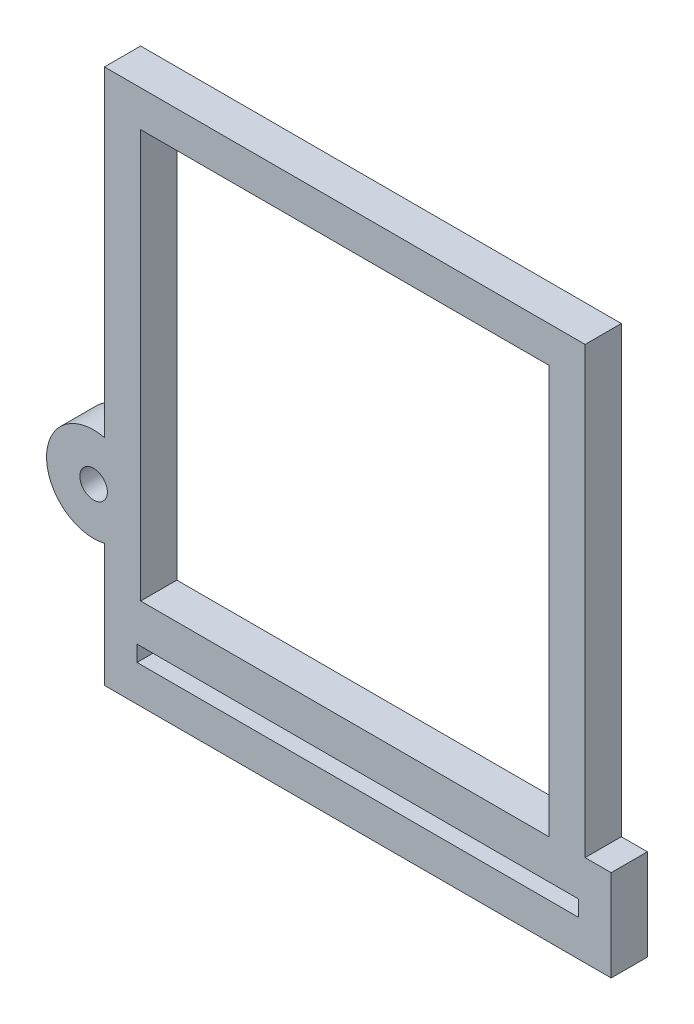
SolidWorks part; units mm, degrees
ref_plane "Спереди" through (0, 0, 0) normal (0, 0, 1) x (1, 0, 0)
ref_plane "Сверху" through (0, 0, 0) normal (0, 1, 0) x (1, 0, 0)
ref_plane "Справа" through (0, 0, 0) normal (1, 0, 0) x (0, 0, -1)
sketch "Эскиз1" plane through (0, 0, 0) normal (0, 0, 1) x (1, 0, 0)
  line L1 (0, 0) -> (70, 0)
  line L2 (0, 0) -> (0, 74)
  line L3 (0, 74) -> (70, 74)
  line L4 (70, 0) -> (70, 74)
  dimension "D1" = 74
  dimension "D2" = 70
extrude "Вытянуть1" add sketch "Эскиз1" along normal blind 5
sketch "Эскиз2" plane through (0, 0, 5) normal (0, 0, 1) x (1, 0, 0)
  line L0 (0, 0) -> (70, 0) construction
  line L1 (4.5, 7.2) -> (65.5, 7.2)
  line L2 (4.5, 7.2) -> (4.5, 5)
  line L3 (4.5, 5) -> (65.5, 5)
  line L4 (65.5, 7.2) -> (65.5, 5)
  dimension "D1" = 61
  dimension "D2" = 4.5
  dimension "D3" = 5
  dimension "D4" = 2.2
extrude "Вытянуть2" cut sketch "Эскиз2" against normal up to next
sketch "Эскиз3" plane through (0, 0, 5) normal (0, 0, 1) x (1, 0, 0)
  line L0 (70, 74) -> (0, 74) construction
  line L1 (5, 69) -> (61.4, 69)
  line L2 (5, 69) -> (5, 12.6)
  line L3 (5, 12.6) -> (61.4, 12.6)
  line L4 (61.4, 69) -> (61.4, 12.6)
  line L5 (0, 74) -> (0, 0) construction
  dimension "D1" = 56.4
  dimension "D2" = 5
  dimension "D3" = 5
extrude "Вытянуть3" cut sketch "Эскиз3" against normal blind 20
sketch "Эскиз4" plane through (0, 0, 0) normal (0, 0, -1) x (-1, 0, 0)
  line L0 (-61.4, 12.6) -> (-5, 12.6) construction
  line L1 (-70, 74) -> (-66.4, 74)
  line L2 (-70, 74) -> (-70, 12.6)
  line L3 (-70, 12.6) -> (-66.4, 12.6)
  line L4 (-66.4, 74) -> (-66.4, 12.6)
  line L5 (-61.4, 69) -> (-61.4, 12.6) construction
  dimension "D1" = 5
extrude "Вытянуть5" cut sketch "Эскиз4" against normal through all
sketch "Эскиз5" plane through (0, 0, 5) normal (0, 0, 1) x (1, 0, 0)
  line L0 (33.2, 12.6) -> (33.2, 69) construction
  line L1 (5, 12.6) -> (61.4, 12.6) construction
  line L2 (61.4, 69) -> (5, 69) construction
  line L3 (61.4, 40.8) -> (5, 40.8) construction
  line L4 (61.4, 12.6) -> (61.4, 69) construction
  line L5 (5, 69) -> (5, 12.6) construction
  circle A0 centre (33.2, 40.8) radius 36 construction
  circle A1 centre (33.2, 40.8) radius 31.35 construction
  circle A2 centre (33.2, 40.8) radius 32.35 construction
  circle A3 centre (-1.5, 23.3291) radius 6.5
  circle A4 centre (-1.5, 23.3291) radius 1.9 construction
  point P12 (33.2, 40.8)
  dimension "D1" = 72
  dimension "D2" = 62.7
  dimension "D3" = 64.7
  dimension "D4" = 3.8
  dimension "D5" = 13
extrude "Вытянуть6" add sketch "Эскиз5" against normal up to surface (5 mm away) up to face at (45.4667, 28.8667, 0)
sketch "Эскиз6" plane through (0, 0, 5) normal (0, 0, 1) x (1, 0, 0)
  circle A0 centre (-1.5, 23.3291) radius 1.9
  arc A1 (0, 29.6537) -> (0, 17.0045) centre (-1.5, 23.3291) ccw construction
  dimension "D1" = 3.8
extrude "Вытянуть7" cut sketch "Эскиз6" against normal up to next
